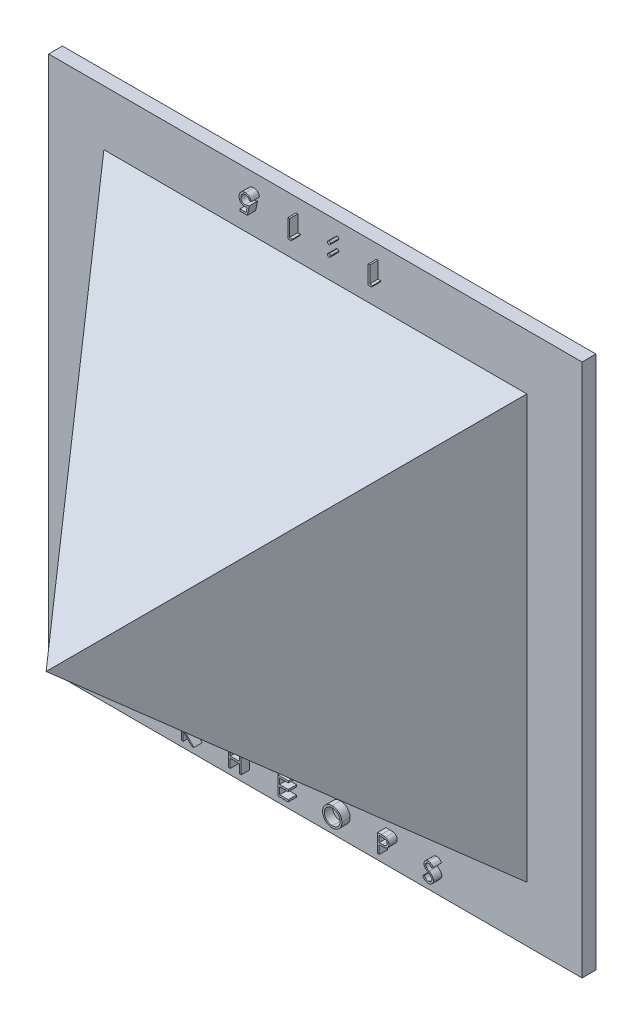
SolidWorks part; units mm, degrees
ref_plane "Plan de face" through (0, 0, 0) normal (0, 0, 1) x (1, 0, 0)
ref_plane "Plan de dessus" through (0, 0, 0) normal (0, 1, 0) x (1, 0, 0)
ref_plane "Plan de droite" through (0, 0, 0) normal (1, 0, 0) x (0, 0, -1)
sketch "Esquisse1" plane through (0, 0, 0) normal (0, 0, 1) x (1, 0, 0)
  line L1 (0, 0) -> (153, 0)
  line L2 (0, 0) -> (0, 153)
  line L3 (0, 153) -> (153, 153)
  line L4 (153, 0) -> (153, 153)
  dimension "D1" = 153
extrude "Boss.-Extru.1" add sketch "Esquisse1" along normal blind 97.7 draft 38.14
sketch "Esquisse3" plane through (0, 0, 0) normal (0, 0, -1) x (-1, 0, 0)
  line L8 (20, -20) -> (20, 173)
  line L9 (20, 173) -> (-173, 173)
  line L10 (-173, 173) -> (-173, -20)
  line L11 (-173, -20) -> (20, -20)
  line L12 (20, -20) -> (20, 173)
  line L13 (20, 173) -> (-173, 173)
  line L14 (-173, 173) -> (-173, -20)
  line L15 (-173, -20) -> (20, -20)
  dimension "D1" = 20
extrude "Boss.-Extru.3" add sketch "Esquisse3" along normal blind 5 separate body
sketch "Esquisse2" plane through (0, 0, -5) normal (0, 0, -1) x (-1, 0, 0)
  line L0 (0, 0) -> (-153, 0) construction
  line L1 (0, 153) -> (0, 0) construction
  circle A0 centre (-76.5, 76.5) radius 24
  point P5 (-76.5, 0)
  point P8 (0, 76.5)
  dimension "D1" = 48
extrude "Boss.-Extru.2" [suppressed] add sketch "Esquisse2" along normal blind 30
sketch "Esquisse4" plane through (0, 0, 0) normal (0, 0, 1) x (1, 0, 0)
  line L0 (30.2453, -15) -> (122.7547, -15) construction
  line L2 (173, -20) -> (-20, -20) construction
  line L3 (51.5, 168) -> (101.5, 168) construction
  line L6 (-20, 173) -> (173, 173) construction
  line L7 (153, 153) -> (0, 153) construction
  line L8 (0, 0) -> (153, 0) construction
  text T0 "KHEOPS" font "Century Gothic" height in points 25
  text T1 "1:15" font "Century Gothic" height in points 25
  point P4 (76.5, 0)
  point P5 (76.5, -15)
  point P15 (76.5, 153)
  point P16 (76.5, 168)
  dimension "D1" = 5
  dimension "D2" = 5
  dimension "D3" = 50
extrude "Boss.-Extru.4" add sketch "Esquisse4" along normal blind 3
